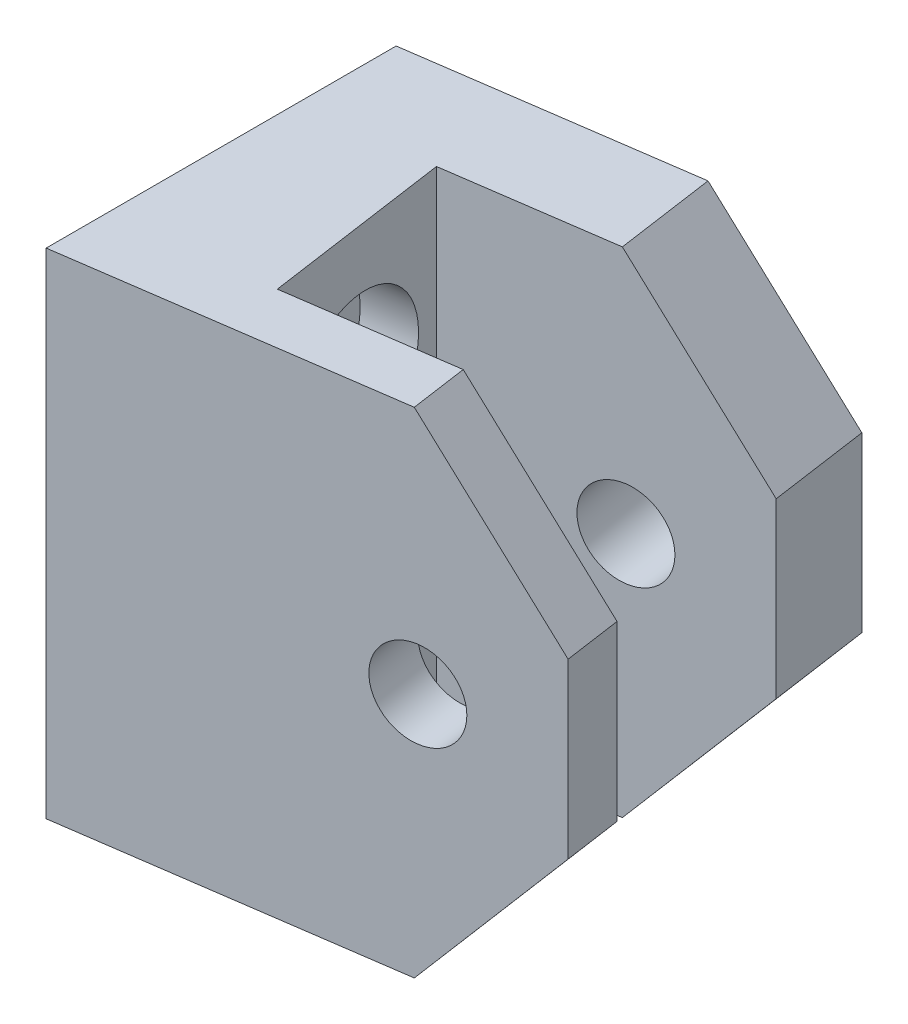
SolidWorks part; units mm, degrees
material "6061-T6 (SS)"
ref_plane "X-Y Datum" through (0, 0, 0) normal (0, 0, 1) x (1, 0, 0)
ref_plane "X-Z Datum" through (0, 0, 0) normal (0, 1, 0) x (1, 0, 0)
ref_plane "Y-Z Datum" through (0, 0, 0) normal (1, 0, 0) x (0, 0, -1)
sketch "Sketch1" plane through (0, 0, 0) normal (0, 1, 0) x (1, 0, 0)
  line L10 (42.9004, 10.9664) -> (-1.905, 4.5379)
  line L11 (31.488, -12.3281) -> (6.9122, -15.8541) construction
  line L12 (31.488, -12.3281) -> (37.2397, -52.4164) construction
  line L13 (47.4113, -20.4743) -> (14.7261, -25.1639)
  line L14 (14.7261, -25.1639) -> (11.7933, -4.723)
  line L15 (11.7933, -4.723) -> (44.4786, -0.0334)
  line L16 (47.4113, -20.4743) -> (48.3132, -26.7599)
  line L17 (48.3132, -26.7599) -> (-0.0216, -33.6948)
  line L19 (44.4786, -0.0334) -> (42.9004, 10.9664)
  line L24 (-1.905, 4.5379) -> (-1.905, -33.8451)
  line L25 (-0.0216, -33.6948) -> (-1.905, -33.965)
  line L26 (-1.905, -33.965) -> (-1.905, -33.8451)
  line L27 (-1.905, 4.5379) -> (-1.905, 90.7516) construction
  line L28 (11.7933, -4.723) -> (-1.905, 90.7516) construction
  point P0 (31.488, -12.3281)
  point P14 (0, 0)
  dimension "D1" = 18.415
  dimension "D2" = 33.393
  dimension "D3" = 50.7324
  dimension "D4" = 8.165
  dimension "D5" = 10.3251
  dimension "D6" = 10.3251
  dimension "D7" = 14.605
  dimension "D8" = 6.35
  dimension "D9" = 11.1125
  dimension "D10" = 21.517
extrude "Boss-Extrude1" add sketch "Sketch1" along normal blind 54.3789
sketch "Sketch6" plane through (4.7364, 0, 33.0121) normal (0.142, 0, 0.9899) x (0.9899, 0, -0.142)
  line L0 (-6.7095, 54.3789) -> (44.023, 54.3789) construction
  line L1 (44.023, 36.7144) -> (29.0719, 54.3789)
  line L2 (44.023, 54.3789) -> (44.023, 0) construction
  line L3 (29.0719, 54.3789) -> (44.023, 54.3789)
  line L4 (44.023, 54.3789) -> (44.023, 36.7144)
  line L5 (29.418, 27.1894) -> (40.6527, 27.1894) construction
  line L6 (44.023, 0) -> (44.023, 17.6644)
  line L7 (29.0719, 0) -> (44.023, 0)
  line L8 (44.023, 17.6644) -> (29.0719, 0)
  circle A0 centre (29.418, 27.1894) radius 4.7625
  dimension "D1" = 9.525
  dimension "D2" = 27.1894
  dimension "D3" = 19.05
extrude "Cut-Extrude2" cut sketch "Sketch6" against normal through all
sketch "Sketch16" plane through (10.8914, 0, -1.5627) normal (0.9899, 0, -0.142) x (-0.142, 0, -0.9899)
  line L0 (-27.0002, 27.1894) -> (-6.35, 27.1894) construction
  line L1 (-16.6751, 54.3789) -> (-16.6751, 0) construction
  line L4 (-27.0002, 0) -> (-6.35, 0)
  line L5 (-6.35, 0) -> (-6.35, 54.3789)
  line L6 (-6.35, 54.3789) -> (-27.0002, 54.3789)
  line L7 (-27.0002, 54.3789) -> (-27.0002, 0)
  line L8 (-27.0002, 0) -> (-6.35, 0) construction
  line L9 (-6.35, 0) -> (-6.35, 54.3789) construction
  line L10 (-6.35, 54.3789) -> (-27.0002, 54.3789) construction
  line L11 (-27.0002, 54.3789) -> (-27.0002, 0) construction
  point P8 (-16.6751, 14.4894)
  point P9 (-16.6751, 39.8894)
  dimension "D2" = 12.7
  dimension "D3" = 25.4
  dimension "D1" = 0
hole_wizard "CBORE for M8 Hex Head Bolt1" positions "Sketch17" profile "Sketch18" counterbore size "M8" standard "ANSI Metric" end condition through all
sketch "Sketch17" plane through (10.8914, 0, -1.5627) normal (0.9899, 0, -0.142) x (-0.142, 0, -0.9899)
  point P0 (-16.6751, 39.8894)
  point P3 (-16.6751, 14.4894)
sketch "Sketch18" plane through (13.2597, 39.8894, 14.9434) normal (0, 1, 0) x (-0.142, 0, -0.9899)
  line L0 (0, 0) -> (0, 17.7124)
  line L1 (0, 17.7124) -> (4.5, 17.7124)
  line L3 (4.5, 17.7124) -> (4.5, 5.68)
  line L4 (4.5, 5.68) -> (8, 5.68)
  line L5 (8, 5.68) -> (8, 0)
  line L7 (8, 0) -> (0, 0)
  line L11 (0, -6.35) -> (0, 107.95) construction
  dimension "Thru Hole Dia." = 9
  dimension "Thru Hole Depth" = 17.7124
  dimension "C'Bore Dia." = 16
  dimension "C'Bore Depth" = 5.68
